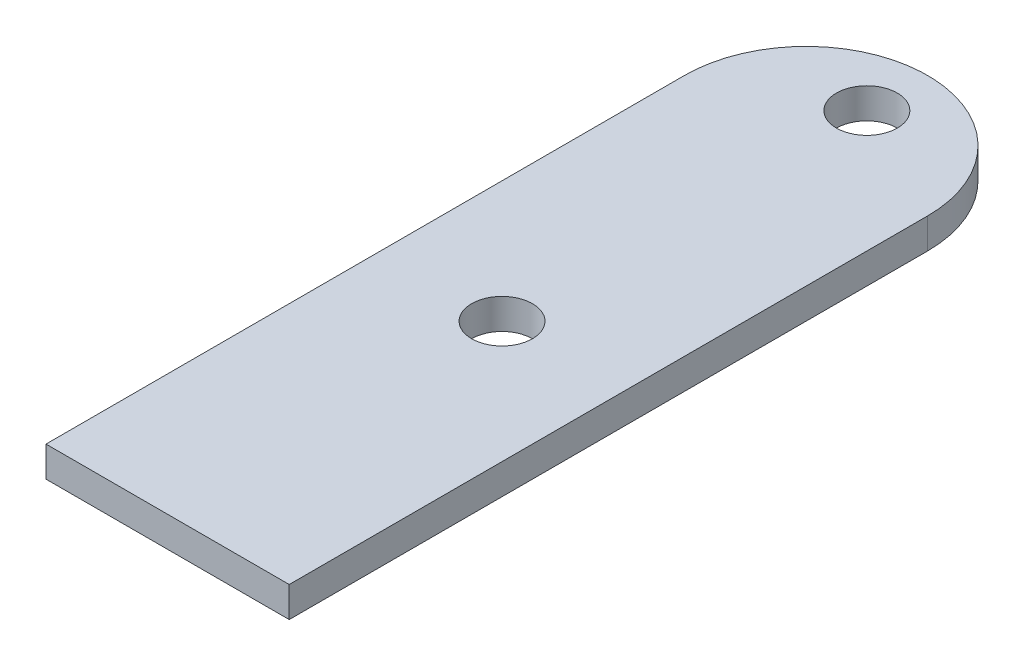
SolidWorks part; units mm, degrees
ref_plane "Front Plane" through (0, 0, 0) normal (0, 0, 1) x (1, 0, 0)
ref_plane "Top Plane" through (0, 0, 0) normal (0, 1, 0) x (1, 0, 0)
ref_plane "Right Plane" through (0, 0, 0) normal (1, 0, 0) x (0, 0, -1)
sketch "Sketch1" plane through (0, 0, 0) normal (0, 1, 0) x (1, 0, 0)
  line L1 (0, 0) -> (25.4, 0)
  line L2 (0, 0) -> (0, 79.375)
  line L3 (0, 79.375) -> (25.4, 79.375)
  line L4 (25.4, 0) -> (25.4, 79.375)
  circle A0 centre (12.7, 73.025) radius 3.175
  circle A1 centre (12.7, 34.925) radius 3.175
  point P12 (12.7, 79.375)
  dimension "D3" = 6.35
  dimension "D4" = 38.1
  dimension "D1" = 25.4
  dimension "D2" = 34.925
  dimension "D5" = 6.35
extrude "Boss-Extrude1" add sketch "Sketch1" along normal blind 3.175
fillet "Fillet1" 2 edges at (0, 1.5875, -79.375) (25.4, 1.5875, -79.375) type full round first side face at (0, 1.5875, -39.6875) second side face at (25.4, 1.5875, -39.6875) middle face at (12.7, 1.5875, -79.375)
